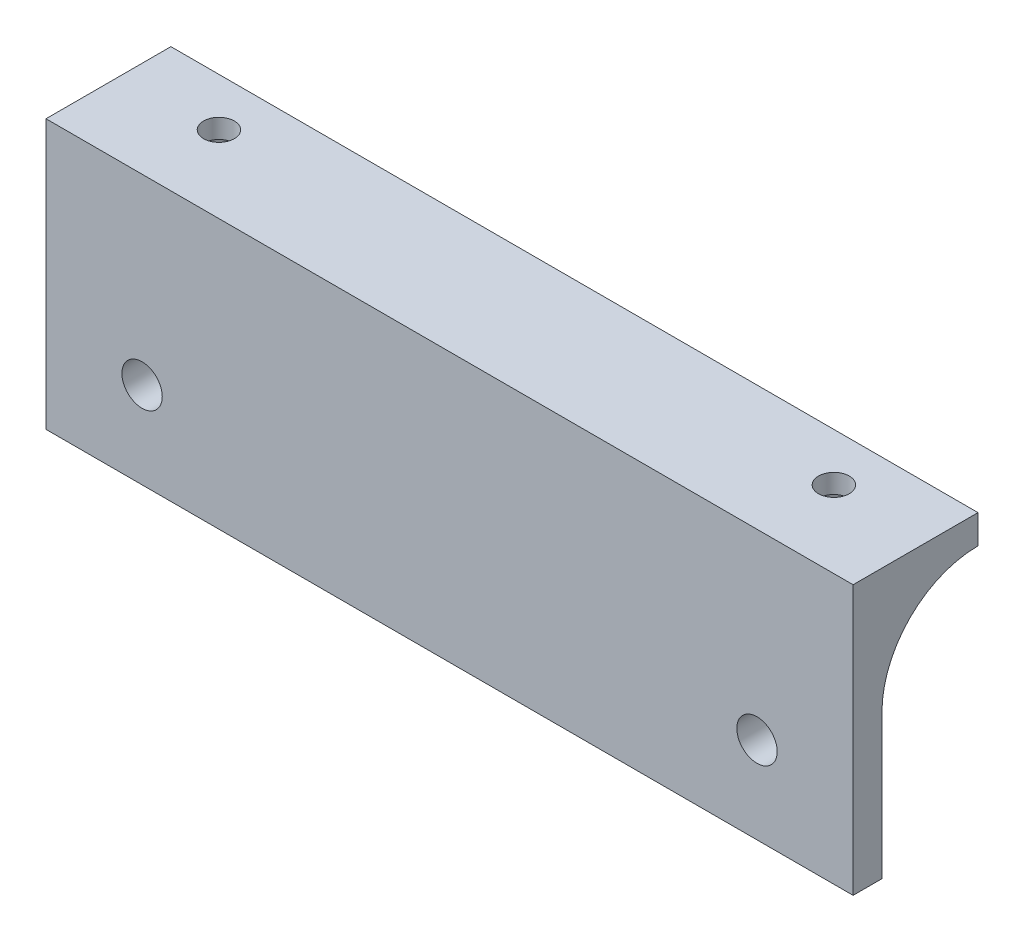
SolidWorks part; units mm, degrees
ref_plane "Front Plane" through (0, 0, 0) normal (0, 0, 1) x (1, 0, 0)
ref_plane "Top Plane" through (0, 0, 0) normal (0, 1, 0) x (1, 0, 0)
ref_plane "Right Plane" through (0, 0, 0) normal (1, 0, 0) x (0, 0, -1)
sketch "Rigidbot" plane through (0, 0, 0) normal (0, 0, 1) x (1, 0, 0)
  line L0 (-42, -5) -> (42, -5) construction
  line L1 (-42, 14) -> (42, 14)
  line L2 (-42, 14) -> (-42, -14)
  line L3 (-42, -14) -> (42, -14)
  line L4 (42, 14) -> (42, -14)
  line L5 (-42, 14) -> (42, -14) construction
  line L6 (-42, -14) -> (42, 14) construction
  line L7 (0, 14) -> (0, -14) construction
  circle A0 centre (-32, -5) radius 2.1
  circle A1 centre (32, -5) radius 2.1
  point P0 (0, 0)
  dimension "D3" = 4.2
  dimension "D1" = 84
  dimension "D2" = 64
  dimension "D4" = 9
  dimension "D5" = 28
extrude "Boss-Rigidbot" add sketch "Rigidbot" along normal blind 3
sketch "Case" plane through (0, 14, 0) normal (0, 1, 0) x (1, 0, 0)
  line L0 (-42, -3) -> (42, -3)
  line L1 (42, -3) -> (42, 10)
  line L2 (42, 10) -> (-42, 10)
  line L3 (-42, 10) -> (-42, -3)
  line L4 (-42, 5) -> (42, 5) construction
  line L5 (0, 10) -> (0, -3) construction
  circle A0 centre (-32, 5) radius 1.6
  circle A1 centre (32, 5) radius 1.6
  dimension "D1" = 3.2
  dimension "D2" = 64
  dimension "D3" = 5
  dimension "D4" = 8
extrude "Boss-Case" add sketch "Case" against normal blind 3
sketch "M3Nut" plane through (0, 14, 0) normal (0, 1, 0) x (1, 0, 0)
  line L0 (0, 10) -> (0, -3) construction
  line L1 (-28.7668, 5) -> (-30.3834, 7.8)
  line L2 (-30.3834, 7.8) -> (-33.6166, 7.8)
  line L3 (-33.6166, 7.8) -> (-35.2332, 5)
  line L4 (-35.2332, 5) -> (-33.6166, 2.2)
  line L5 (-33.6166, 2.2) -> (-30.3834, 2.2)
  line L6 (-30.3834, 2.2) -> (-28.7668, 5)
  line L7 (42, 10) -> (-42, 10) construction
  line L8 (42, -3) -> (-42, -3) construction
  line L9 (30.3834, 2.2) -> (28.7668, 5)
  line L10 (33.6166, 2.2) -> (30.3834, 2.2)
  line L11 (35.2332, 5) -> (33.6166, 2.2)
  line L12 (33.6166, 7.8) -> (35.2332, 5)
  line L13 (30.3834, 7.8) -> (33.6166, 7.8)
  line L14 (28.7668, 5) -> (30.3834, 7.8)
  circle A0 centre (-32, 5) radius 2.8 construction
  circle A1 centre (32, 5) radius 2.8 construction
  dimension "D1" = 5.6
extrude "Cut-M3Nut" cut sketch "M3Nut" against normal blind 10 from offset 2 offset against normal yes
fillet "Fillet" radius 10 1 edges at (0, 11, 0)
